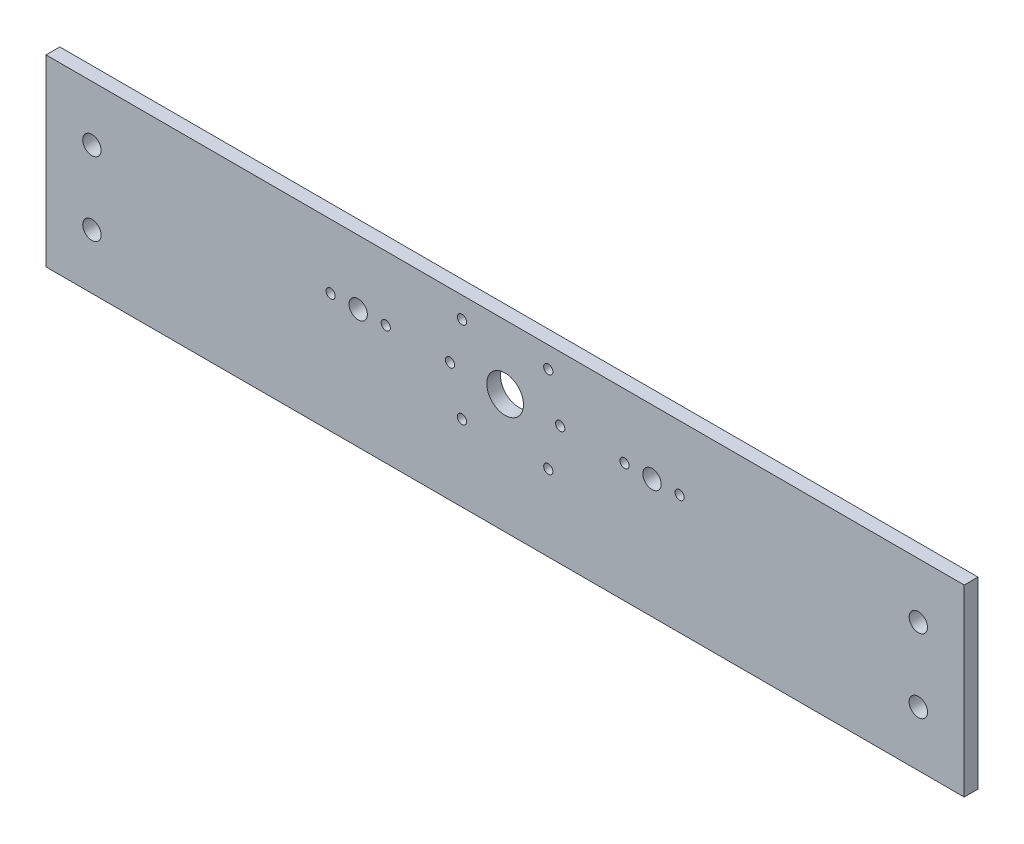
SolidWorks part; units mm, degrees
ref_plane "Front Plane" through (0, 0, 0) normal (0, 0, 1) x (1, 0, 0)
ref_plane "Top Plane" through (0, 0, 0) normal (0, 1, 0) x (1, 0, 0)
ref_plane "Right Plane" through (0, 0, 0) normal (1, 0, 0) x (0, 0, -1)
sketch "Sketch2" plane through (0, 0, 0) normal (0, 0, 1) x (1, 0, 0)
  line L1 (0, 100) -> (500, 100)
  line L2 (0, 100) -> (0, 0)
  line L3 (0, 0) -> (500, 0)
  line L4 (500, 100) -> (500, 0)
  dimension "D1" = 100
  dimension "D2" = 500
extrude "Boss-Extrude1" add sketch "Sketch2" along normal blind 7.5
sketch "Sketch9" plane through (0, 0, 7.5) normal (0, 0, 1) x (1, 0, 0)
  line L0 (500, 100) -> (0, 100) construction
  circle A0 centre (170, 65) radius 5
  circle A1 centre (185, 65) radius 2.5
  circle A2 centre (155, 65) radius 2.5
  circle A3 centre (330, 65) radius 5
  circle A4 centre (345, 65) radius 2.5
  circle A5 centre (315, 65) radius 2.5
  circle A6 centre (250, 65) radius 10
  circle A7 centre (280, 65) radius 2.5
  circle A8 centre (220, 65) radius 2.5
  circle A9 centre (226.5, 88.5) radius 2.5
  circle A10 centre (273.5, 88.5) radius 2.5
  circle A11 centre (273.5, 41.5) radius 2.5
  circle A12 centre (226.5, 41.5) radius 2.5
  dimension "D1" = 35
  dimension "D2" = 2
  dimension "D3" = 2
extrude "Cut-Extrude3" cut sketch "Sketch9" against normal through all
sketch "Sketch11" plane through (0, 0, 7.5) normal (0, 0, 1) x (1, 0, 0)
  line L0 (500, 100) -> (0, 100) construction
  line L1 (0, 0) -> (500, 0) construction
  line L2 (0, 100) -> (0, 0) construction
  line L3 (500, 0) -> (500, 100) construction
  circle A0 centre (25, 70) radius 5
  circle A1 centre (25, 30) radius 5
  circle A2 centre (475, 30) radius 5
  circle A3 centre (475, 70) radius 5
  dimension "D1" = 40
  dimension "D3" = 30
  dimension "D2" = 40
  dimension "D4" = 30
  dimension "D5" = 30
  dimension "D6" = 30
  dimension "D7" = 25
  dimension "D8" = 25
extrude "Cut-Extrude4" cut sketch "Sketch11" against normal through all
